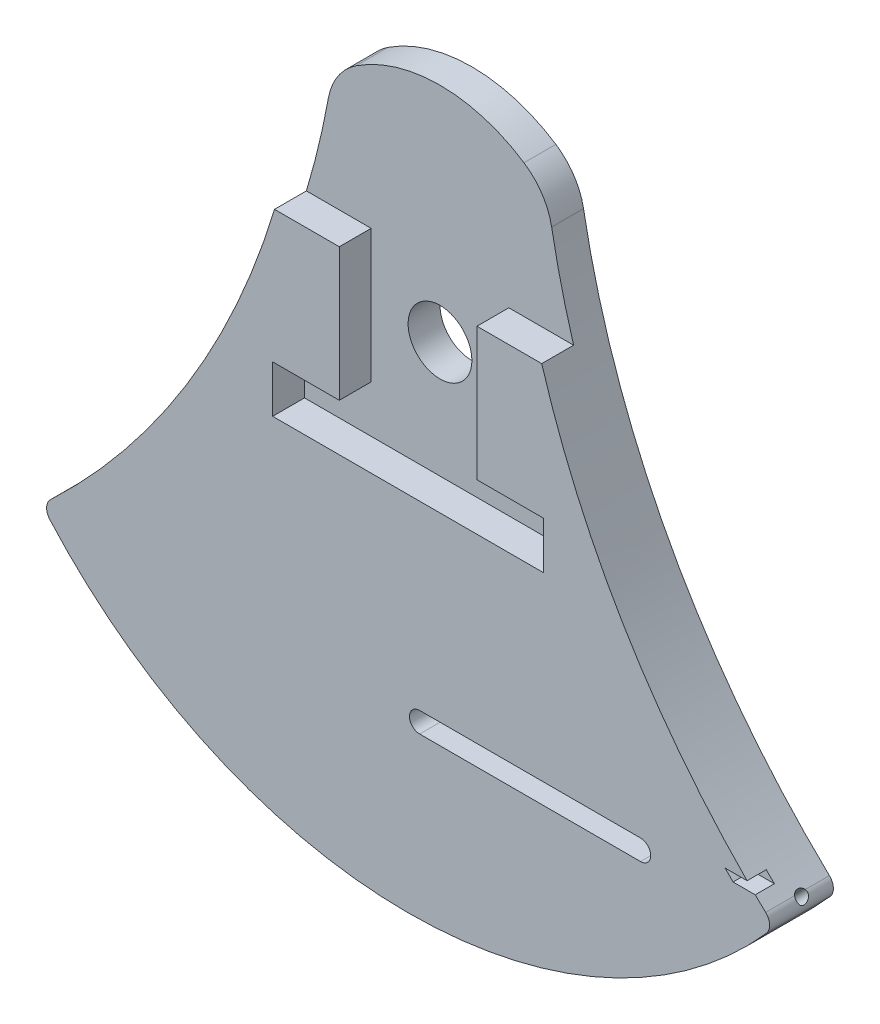
SolidWorks part; units mm, degrees
ref_plane "Front Plane" through (0, 0, 0) normal (0, 0, 1) x (1, 0, 0)
ref_plane "Top Plane" through (0, 0, 0) normal (0, 1, 0) x (1, 0, 0)
ref_plane "Right Plane" through (0, 0, 0) normal (1, 0, 0) x (0, 0, -1)
sketch "Sketch1" plane through (0, 0, 0) normal (0, 0, 1) x (1, 0, 0)
  line L0 (0, 0) -> (0, 60) construction
  line L1 (-53.033, -53.033) -> (0, 0) construction
  line L2 (0, 60) -> (16, 60) construction
  line L3 (0, 60) -> (0, 50) construction
  line L4 (0, 60) -> (-16, 60) construction
  line L5 (0, 0) -> (0, -95.7808) construction
  line L6 (0, 0) -> (53.033, -53.033) construction
  line L8 (-64.561, -58.9899) -> (67.8775, -58.9899) construction
  line L9 (-21.2432, 10.0603) -> (-10.7929, 10.0603) construction
  line L10 (-10.7929, 10.0603) -> (-10.7929, -10.7929) construction
  line L11 (-10.7929, -10.7929) -> (-21.2412, -10.7929) construction
  line L12 (-21.2412, -10.7929) -> (-21.2412, -18.1924) construction
  line L13 (21.2412, -10.7929) -> (21.2412, -18.1924) construction
  line L14 (10.7929, -10.7929) -> (21.2412, -10.7929) construction
  line L15 (10.7929, 10.0603) -> (10.7929, -10.7929) construction
  line L16 (21.2432, 10.0603) -> (10.7929, 10.0603) construction
  line L17 (-21.2412, -18.1924) -> (21.2412, -18.1924) construction
  line L18 (-63.2289, -53.033) -> (63.2289, -53.033) construction
  line L19 (0, 0) -> (-57.4533, -48.2091) construction
  line L20 (0, 0) -> (57.4533, -48.2091) construction
  circle A0 centre (0, 0) radius 5 construction
  arc A1 (-57.4533, -48.2091) -> (-16, 60) centre (-145.6998, 47.6415) ccw
  arc A2 (57.4533, -48.2091) -> (16, 60) centre (145.6998, 47.6415) cw
  arc A3 (-16, 60) -> (16, 60) centre (0, 58.8889) cw
  arc A5 (57.4533, -48.2091) -> (-57.4533, -48.2091) centre (0, 0) cw
  point P20 (0, -106.066)
  dimension "D1" = 10
  dimension "D2" = 75
  dimension "D3" = 60
  dimension "D4" = 5
  dimension "D5" = 5
extrude "Body" add sketch "Sketch1" along normal blind 10
sketch "Sketch2" plane through (0, 0, 10) normal (0, 0, 1) x (1, 0, 0)
  circle A0 centre (0, 0) radius 5
  dimension "D1" = 10
extrude "Attachment Hole" cut sketch "Sketch2" against normal through all
sketch "Sketch17" plane through (0, 0, 10) normal (0, 0, 1) x (1, 0, 0)
  line L0 (-21.2432, 10.0603) -> (-10.7929, 10.0603)
  line L1 (-10.7929, 10.0603) -> (-10.7929, -10.7929)
  line L2 (-10.7929, -10.7929) -> (-21.2412, -10.7929)
  line L3 (-21.2412, -10.7929) -> (-21.2412, -18.1924)
  line L4 (-21.2412, -18.1924) -> (21.2412, -18.1924)
  line L5 (21.2412, -18.1924) -> (21.2412, -10.7929)
  line L6 (21.2412, -10.7929) -> (10.7929, -10.7929)
  line L7 (10.7929, -10.7929) -> (10.7929, 10.0603)
  line L8 (10.7929, 10.0603) -> (21.2432, 10.0603)
  line L9 (0, 0) -> (0, 42.2888) construction
  line L10 (0, 0) -> (0, 60) construction
  arc A0 (-21.2432, 10.0603) -> (-16.9187, 27.8879) centre (-174.7002, 56.723) ccw
  arc A1 (-57.4533, -48.2091) -> (-16, 60) centre (-145.6998, 47.6415) ccw construction
  arc A2 (21.2432, 10.0603) -> (16.9187, 27.8879) centre (174.7002, 56.723) cw
  arc A3 (-16.9187, 27.8879) -> (16.9187, 27.8879) centre (0, 10.9692) cw
sketch "Sketch20" plane through (0, 0, 10) normal (0, 0, 1) x (1, 0, 0)
  arc A0 (-57.4533, -48.2091) -> (57.4533, -48.2091) centre (0, 0) ccw construction
  point P0 (0, -75)
ref_plane "Plane1" through (0, -75, 10) normal (0, -1, 0) x (-1, 0, 0)
ref_plane "Plane2" through (0, -58.9899, 0) normal (0, -1, 0) x (-1, 0, 0)
sketch "Sketch21" plane through (0, -58.9899, 0) normal (0, -1, 0) x (-1, 0, 0)
  line L0 (-57.4533, -10) -> (57.4533, -10) construction
  line L1 (-53.5312, -6.1608) -> (-60.3001, -6.1608) construction
  line L2 (-60.3001, -6.1608) -> (-60.3001, -3.8392) construction
  line L3 (-60.3001, -3.8392) -> (-53.5312, -3.8392) construction
  line L4 (-53.5312, -3.8392) -> (-53.5312, -6.1608) construction
  line L5 (-53.5312, -5) -> (-60.3001, -5) construction
  circle A0 centre (53.297, -5.3768) radius 0.9038
  dimension "D3" = 1.8076
  dimension "D2" = 5
sketch "Sketch22" plane through (0, -75, 10) normal (0, -1, 0) x (-1, 0, 0)
  line L4 (51.4588, 8.1358) -> (51.4588, 1.7252)
  line L5 (51.4588, 1.7252) -> (-59.5848, 1.7252)
  line L6 (-59.5848, 1.7252) -> (-59.5848, 8.1358)
  line L7 (-59.5848, 8.1358) -> (51.4588, 8.1358)
wrap "Wrap1" sketch "Sketch22" wrap type deboss source sketch "Sketch22" thickness 3 face at (0, -61.6045, 5) parameters "D1"=3
sketch "Sketch23" plane through (0, 0, 10) normal (0, 0, 1) x (1, 0, 0)
  line L0 (-57.4533, -48.2091) -> (57.4533, -48.2091) construction
  line L1 (1.8121, -48.2091) -> (36.4412, -48.2091) construction
  line L2 (1.8121, -46.6091) -> (36.4412, -46.6091)
  line L3 (1.8121, -49.8091) -> (36.4412, -49.8091)
  arc A0 (1.8121, -46.6091) -> (1.8121, -49.8091) centre (1.8121, -48.2091) ccw
  arc A1 (36.4412, -49.8091) -> (36.4412, -46.6091) centre (36.4412, -48.2091) ccw
  point P6 (19.1266, -48.2091)
  dimension "D1" = 3.2
fillet "Fillet3" radius 2 1 edges at (-57.4533, -48.2091, 5)
fillet "Fillet4" radius 2 1 edges at (57.4533, -48.2091, 5)
extrude "Horiz Slot" cut sketch "Sketch23" against normal through all
sketch "Sketch26" plane through (0, 0, 10) normal (0, 0, 1) x (1, 0, 0)
  line L0 (54.4274, -45.3322) -> (50.9516, -45.3322)
  line L1 (54.4274, -45.3322) -> (53.1505, -44.0613)
  line L2 (53.1505, -44.0613) -> (49.7, -44.0613)
  line L3 (49.7, -44.0613) -> (50.9516, -45.3322)
  arc A0 (16, 60) -> (56.0605, -46.9078) centre (145.6998, 47.6415) ccw construction
extrude "Cut-Extrude15" cut sketch "Sketch26" against normal blind 3
sketch "Sketch27" plane through (0, 0, 10) normal (0, 0, 1) x (1, 0, 0)
  arc A0 (-16.9187, 27.8879) -> (-16, 60) centre (-145.6998, 47.6415) ccw
  arc A1 (-16, 60) -> (16, 60) centre (0, 58.8889) cw
  arc A2 (16, 60) -> (16.9187, 27.8879) centre (145.6998, 47.6415) ccw
  arc A3 (-16.9187, 27.8879) -> (16.9187, 27.8879) centre (0, 10.9692) cw
extrude "Cut-Extrude16" cut sketch "Sketch27" against normal through all
extrude "Cut-Extrude17" cut sketch "Sketch17" against normal blind 5
sketch "Sketch29" plane through (0, 0, 10) normal (0, 0, 1) x (1, 0, 0)
  line L0 (-70.3279, -28.5857) -> (12.4268, -28.5857) construction
ref_plane "Plane3" through (0, -28.5857, 0) normal (0, -1, 0) x (-1, 0, 0)
fillet "Fillet5" radius 10 2 edges at (16.9187, 27.8879, 2.5) (-16.9187, 27.8879, 2.5)
sketch "Sketch31" plane through (0, 0, 0) normal (-0.7007, -0.7135, 0) x (0.7135, -0.7007, 0)
  circle A0 centre (73.324, 4.6195) radius 0.95
  dimension "D1" = 1.9
extrude "Cut-Extrude24" cut sketch "Sketch31" against normal through all
extrude "Cut-Extrude25" cut sketch "Sketch21" against normal through all contours A0
sketch "Sketch32" plane through (0, -58.9899, 0) normal (0, -1, 0) x (-1, 0, 0)
  circle A0 centre (53.297, -6.3768) radius 1.7
sketch "Sketch33" plane through (0, -28.5857, 0) normal (0, -1, 0) x (-1, 0, 0)
  circle A0 centre (53.297, -5.3768) radius 1.625
  dimension "D1" = 3.25
extrude "Cut-Extrude27" cut sketch "Sketch33" along normal blind 22.35
